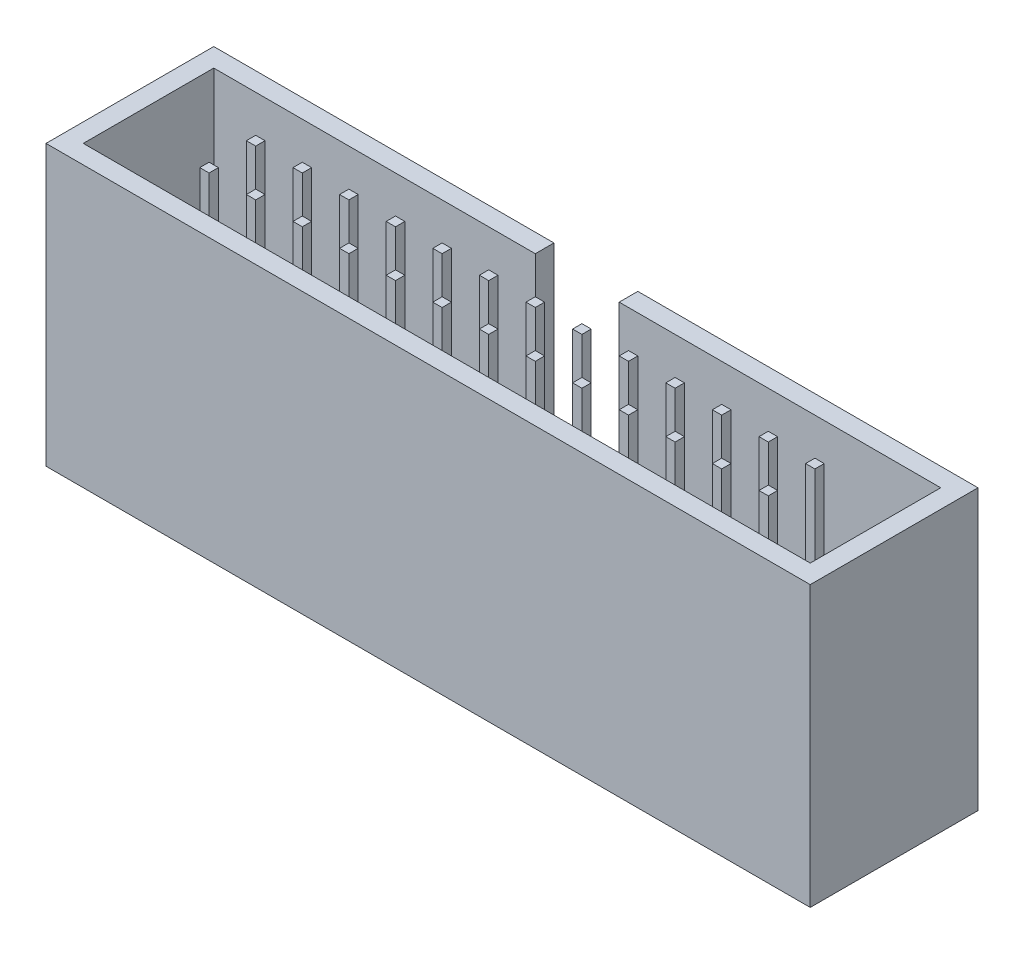
SolidWorks part; units mm, degrees
material "聚脂树脂"
ref_plane "前视基准面" through (0, 0, 0) normal (0, 0, 1) x (1, 0, 0)
ref_plane "上视基准面" through (0, 0, 0) normal (0, 1, 0) x (1, 0, 0)
ref_plane "右视基准面" through (0, 0, 0) normal (1, 0, 0) x (0, 0, -1)
sketch "底图" plane through (0, 0, 0) normal (0, 1, 0) x (1, 0, 0)
  line L1 (19.5, -3.5) -> (-19.5, -3.5)
  line L2 (19.5, -3.5) -> (19.5, 3.5)
  line L3 (19.5, 3.5) -> (-19.5, 3.5)
  line L4 (-19.5, -3.5) -> (-19.5, 3.5)
  line L5 (19.5, -3.5) -> (-19.5, 3.5) construction
  line L6 (19.5, 3.5) -> (-19.5, -3.5) construction
  line L7 (20.5, -4.5) -> (-20.5, -4.5)
  line L8 (20.5, -4.5) -> (20.5, 4.5)
  line L9 (20.5, 4.5) -> (-20.5, 4.5)
  line L10 (-20.5, -4.5) -> (-20.5, 4.5)
  line L11 (20.5, -4.5) -> (-20.5, 4.5) construction
  line L12 (20.5, 4.5) -> (-20.5, -4.5) construction
  line L13 (2.25, -4.5) -> (-2.25, -4.5)
  line L14 (2.25, -4.5) -> (2.25, 4.5)
  line L15 (2.25, 4.5) -> (-2.25, 4.5)
  line L16 (-2.25, -4.5) -> (-2.25, 4.5)
  line L17 (2.25, -4.5) -> (-2.25, 4.5) construction
  line L18 (2.25, 4.5) -> (-2.25, -4.5) construction
  line L19 (-15, -1.25) -> (15, -1.25)
  line L20 (-15, -1.25) -> (-15, 1.25)
  line L21 (-15, 1.25) -> (15, 1.25)
  line L22 (15, -1.25) -> (15, 1.25)
  line L23 (-15, -1.25) -> (15, 1.25) construction
  line L24 (-15, 1.25) -> (15, -1.25) construction
  point P0 (0, 0)
  point P6 (0, 0)
  point P11 (0, 0)
  point P16 (0, 0)
  dimension "D1" = 7
  dimension "D2" = 39
  dimension "D3" = 41
  dimension "D4" = 9
  dimension "D5" = 4.5
  dimension "D6" = 9
  dimension "D7" = 2.5
  dimension "D8" = 30
sketch "基体" plane through (0, 0, 0) normal (0, 1, 0) x (1, 0, 0)
  line L4 (-2.25, -4.5) -> (2.25, -4.5)
  line L5 (-2.25, 4.5) -> (-2.25, -4.5)
  line L6 (2.25, 4.5) -> (-2.25, 4.5)
  line L7 (2.25, -4.5) -> (2.25, 4.5)
  line L8 (-2.25, -4.5) -> (2.25, -4.5)
  line L10 (2.25, 4.5) -> (-2.25, 4.5)
  line L12 (-20.5, -4.5) -> (20.5, -4.5)
  line L13 (-20.5, 4.5) -> (-20.5, -4.5)
  line L14 (20.5, 4.5) -> (-20.5, 4.5)
  line L15 (20.5, -4.5) -> (20.5, 4.5)
  line L16 (-20.5, -4.5) -> (20.5, -4.5)
  line L17 (-20.5, 4.5) -> (-20.5, -4.5)
  line L18 (20.5, 4.5) -> (-20.5, 4.5)
  line L19 (20.5, -4.5) -> (20.5, 4.5)
  dimension "D1" = 0
  dimension "D2" = 0
extrude "基体-凸台-拉伸" add sketch "基体" along normal blind 15 contours L16 L19 L18 L10 L17 L8 region at (0, 0, 0) region at (-11.375, 0, 0) region at (11.375, 0, 0)
sketch "草图4" plane through (0, 0, 0) normal (0, 1, 0) x (1, 0, 0)
  line L1 (19.5, -3.5) -> (-19.5, -3.5)
  line L2 (19.5, -3.5) -> (19.5, 3.5)
  line L3 (19.5, 3.5) -> (-19.5, 3.5)
  line L4 (-19.5, -3.5) -> (-19.5, 3.5)
  line L5 (19.5, -3.5) -> (-19.5, 3.5) construction
  line L6 (19.5, 3.5) -> (-19.5, -3.5) construction
  point P0 (0, 0)
  dimension "D1" = 7
  dimension "D2" = 39
extrude "切除-拉伸8" cut sketch "草图4" against normal blind 10 from offset 15
sketch "草图5" plane through (0, 15, 0) normal (0, 1, 0) x (1, 0, 0)
  line L0 (-2.25, 0) -> (2.25, 0)
  line L2 (2.25, 0) -> (2.25, 6.901)
  line L3 (2.25, 6.901) -> (-2.25, 6.901)
  line L4 (-2.25, 0) -> (-2.25, 6.901)
  line L5 (0, 0) -> (-2.25, 6.901) construction
  line L6 (2.25, 6.901) -> (0, 0) construction
  point P0 (0, 0)
  dimension "D1" = 4.5
extrude "切除-拉伸9" cut sketch "草图5" against normal blind 10
sketch "草图6" plane through (0, 5, 0) normal (0, 1, 0) x (1, 0, 0)
  line L1 (0.25, 1) -> (-0.25, 1)
  line L10 (0.25, 1) -> (0.25, 1.5)
  line L11 (0.25, 1.5) -> (-0.25, 1.5)
  line L12 (-0.25, 1) -> (-0.25, 1.5)
  line L13 (0.25, 1) -> (-0.25, 1.5) construction
  line L14 (0.25, 1.5) -> (-0.25, 1) construction
  dimension "D1" = 0.5
  dimension "D2" = 0.5
  dimension "D3" = 1.5
extrude "Extrude1" add sketch "草图6" along normal blind 10
pattern_linear "LPattern1" count 7 spacing 2.5 along (1, 0, 0) count 7 spacing 2.5 along (-1, 0, 0) of "Extrude1"
mirror "Mirror1" about plane through (0, 0, 0) normal (0, 0, 1) of "LPattern1"
